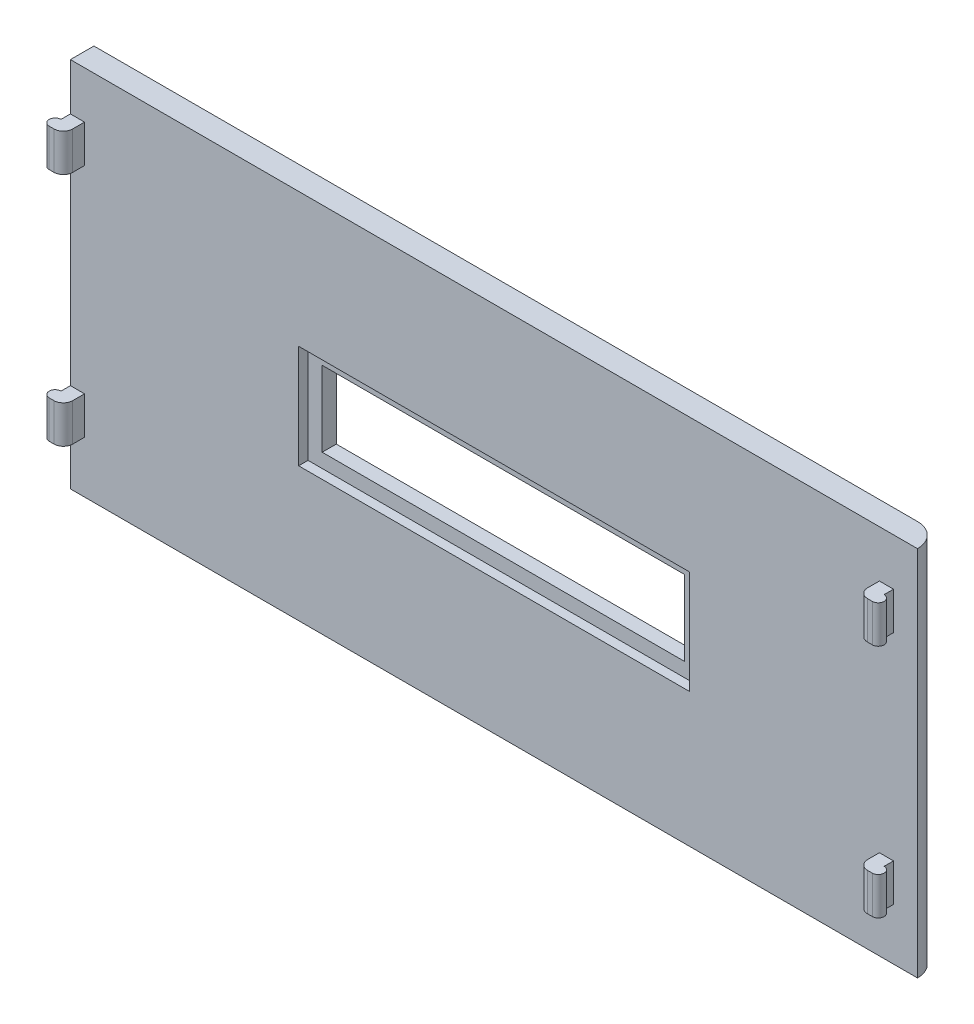
SolidWorks part; units mm, degrees
ref_plane "Front Plane" through (0, 0, 0) normal (0, 0, 1) x (1, 0, 0)
ref_plane "Top Plane" through (0, 0, 0) normal (0, 1, 0) x (1, 0, 0)
ref_plane "Right Plane" through (0, 0, 0) normal (1, 0, 0) x (0, 0, -1)
sketch "Sketch1" plane through (0, 0, 0) normal (0, 0, 1) x (1, 0, 0)
  line L1 (-90, -39.5) -> (90, -39.5)
  line L2 (-90, -39.5) -> (-90, 39.5)
  line L3 (-90, 39.5) -> (90, 39.5)
  line L4 (90, -39.5) -> (90, 39.5)
  line L5 (-90, -39.5) -> (90, 39.5) construction
  line L6 (-90, 39.5) -> (90, -39.5) construction
  point P0 (0, 0)
  dimension "D1" = 180
  dimension "D2" = 79
extrude "Boss-Extrude1" add sketch "Sketch1" along normal blind 5
fillet "Fillet1" radius 5 1 edges at (90, 0, 0)
sketch "Sketch2" plane through (0, 0, 5) normal (0, 0, 1) x (1, 0, 0)
  line L0 (-90, 39.5) -> (-90, -39.5) construction
  line L1 (-90, -20.5) -> (-87, -20.5)
  line L2 (-90, -20.5) -> (-90, -28.5)
  line L3 (-90, -28.5) -> (-87, -28.5)
  line L4 (-87, -20.5) -> (-87, -28.5)
  line L5 (90, 39.5) -> (-90, 39.5) construction
  line L6 (-90, 29.5) -> (-87, 29.5)
  line L7 (-90, 29.5) -> (-90, 21.5)
  line L8 (-90, 21.5) -> (-87, 21.5)
  line L9 (-87, 29.5) -> (-87, 21.5)
  line L10 (84.9, 29.5) -> (81.9, 29.5)
  line L11 (84.9, 29.5) -> (84.9, 21.5)
  line L12 (84.9, 21.5) -> (81.9, 21.5)
  line L13 (81.9, 29.5) -> (81.9, 21.5)
  line L14 (84.9, -20.5) -> (81.9, -20.5)
  line L15 (84.9, -20.5) -> (84.9, -28.5)
  line L16 (84.9, -28.5) -> (81.9, -28.5)
  line L17 (81.9, -20.5) -> (81.9, -28.5)
  line L18 (-90, -39.5) -> (90, -39.5) construction
  line L20 (90, -39.5) -> (90, 39.5) construction
  point P18 (-88.5, 29.5)
  dimension "D1" = 10
  dimension "D2" = 8
  dimension "D3" = 3
  dimension "D4" = 11
  dimension "D5" = 8
  dimension "D6" = 3
  dimension "D7" = 11
  dimension "D8" = 8
  dimension "D9" = 3
  dimension "D10" = 5.1
  dimension "D11" = 10
  dimension "D12" = 5.1
  dimension "D13" = 3
  dimension "D14" = 8
extrude "Boss-Extrude2" add sketch "Sketch2" along normal blind 4.5
fillet "Fillet2" radius 2 4 edges at (81.9, -24.5, 9.5) (81.9, 25.5, 9.5) (-87, -24.5, 9.5) (-87, 25.5, 9.5)
sketch "Sketch3" plane through (0, 29.5, 0) normal (0, 1, 0) x (1, 0, 0)
  line L0 (84.9, -9.5) -> (84.9, -5) construction
  circle A0 centre (84.9, -8.25) radius 1.25
  dimension "D1" = 2.5
extrude "Boss-Extrude3" add sketch "Sketch3" against normal blind 8
pattern_linear "LPattern1" count 2 spacing 50 along (0, -1, 0) count 2 spacing 174.9 along (-1, 0, 0) of "Boss-Extrude3"
sketch "Sketch4" plane through (0, 0, 5) normal (0, 0, 1) x (1, 0, 0)
  line L1 (-41.5, -11) -> (41.5, -11)
  line L2 (-41.5, -11) -> (-41.5, 11)
  line L3 (-41.5, 11) -> (41.5, 11)
  line L4 (41.5, -11) -> (41.5, 11)
  line L5 (-41.5, -11) -> (41.5, 11) construction
  line L6 (-41.5, 11) -> (41.5, -11) construction
  point P0 (0, 0)
  dimension "D1" = 83
  dimension "D2" = 22
extrude "Cut-Extrude1" cut sketch "Sketch4" against normal blind 2
sketch "Sketch5" plane through (0, 0, 3) normal (0, 0, 1) x (1, 0, 0)
  line L12 (38.5, -8) -> (38.5, 8)
  line L13 (38.5, 8) -> (-38.5, 8)
  line L14 (-38.5, 8) -> (-38.5, -8)
  line L15 (-38.5, -8) -> (38.5, -8)
  line L16 (38.5, -8) -> (38.5, 8)
  line L17 (38.5, 8) -> (-38.5, 8)
  line L18 (-38.5, 8) -> (-38.5, -8)
  line L19 (-38.5, -8) -> (38.5, -8)
  dimension "D1" = 3
extrude "Cut-Extrude2" cut sketch "Sketch5" against normal blind 3
